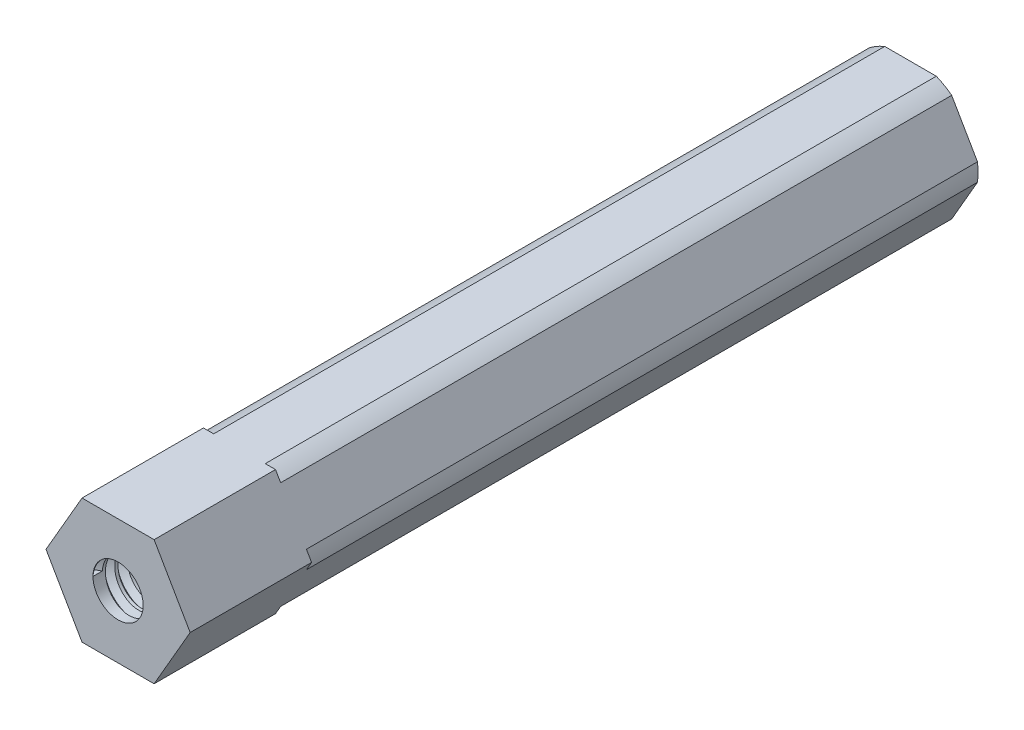
SolidWorks part; units mm, degrees
material "7075-T6 (SN)"
ref_plane "Alzado" through (0, 0, 0) normal (0, 0, 1) x (1, 0, 0)
ref_plane "Planta" through (0, 0, 0) normal (0, 1, 0) x (1, 0, 0)
ref_plane "Vista lateral" through (0, 0, 0) normal (1, 0, 0) x (0, 0, -1)
sketch "Croquis2" plane through (0, 0, 0) normal (0, 0, 1) x (1, 0, 0)
  line L1 (3.6662, -6.35) -> (7.3323, 0)
  line L2 (7.3323, 0) -> (3.6662, 6.35)
  line L3 (3.6662, 6.35) -> (-3.6662, 6.35)
  line L4 (-3.6662, 6.35) -> (-7.3323, 0)
  line L5 (-7.3323, 0) -> (-3.6662, -6.35)
  line L6 (-3.6662, -6.35) -> (3.6662, -6.35)
  circle A0 centre (0, 0) radius 6.35 construction
  dimension "D1" = 12.7
extrude "Extrusión Hex Profile" add sketch "Croquis2" along normal mid plane 80.6132
sketch "Croquis3" plane through (0, 0, 0) normal (0, 0, 1) x (1, 0, 0)
  circle A0 centre (0, 0) radius 2.5527
  dimension "D1" = 5.1054
extrude "Tap Hole 1" cut sketch "Croquis3" against normal blind 19.05 from surface starting at face at (0, 0, 40.3066)
extrude "Tap Hole 2" cut sketch "Croquis3<3>" along normal blind 19.05 from surface starting at face at (0, 0, -40.3066)
sketch "Croquis3<3>" plane through (0, 0, 0) normal (0, 0, 1) x (1, 0, 0) same geometry as "Croquis3"
sketch "Croquis7" plane through (0, 0, 0) normal (0, 0, 1) x (1, 0, 0)
  circle A0 centre (0, 0) radius 6.8707
  dimension "D1" = 13.7414
extrude "ThunderHex" cut sketch "Croquis7" along normal offset from surface (68.2625 mm away) 12.3508 from surface flip side to cut up to face at (2.5527, 0, 40.3066) starting at face at (2.5527, 0, -40.3066)
sketch "Croquis8" plane through (0, 0, 0) normal (0, 1, 0) x (1, 0, 0)
  line L0 (0, -40.3066) -> (-5.5563, -40.3066) construction
  line L1 (3.6662, -40.3066) -> (-3.6662, -40.3066) construction
  line L3 (0, -40.3066) -> (0, 0) construction
  line L4 (-5.5563, -40.3066) -> (-6.35, -39.5129)
  line L5 (-6.35, -39.5129) -> (-6.35, -38.7191)
  line L6 (-6.35, -38.7191) -> (-5.9055, -38.7191)
  line L7 (-5.9055, -38.7191) -> (-5.9055, -37.1316)
  line L8 (-5.9055, -37.1316) -> (-12.7, -37.1316)
  line L9 (-12.7, -37.1316) -> (-12.7, -40.3066)
  line L10 (-12.7, -40.3066) -> (-5.5563, -40.3066)
  line L11 (-3.6662, -40.3066) -> (-7.3323, -40.3066) construction
  dimension "D1" = 11.811
  dimension "D2" = 12.7
  dimension "D3" = 45
  dimension "D4" = 0.7937
  dimension "D6" = 0.7937
  dimension "D7" = 3.175
  dimension "D8" = 25.4
revolve "Retaining Ring 1" [suppressed] cut sketch "Croquis8" angle 360 about L3
sketch "Croquis9" plane through (0, 0, 0) normal (0, -1, 0) x (1, 0, 0)
  line L0 (0, -40.3066) -> (-5.5563, -40.3066) construction
  line L3 (0, -40.3066) -> (0, 0) construction
  line L4 (-5.5563, -40.3066) -> (-6.35, -39.5129)
  line L5 (-6.35, -39.5129) -> (-6.35, -38.7191)
  line L6 (-6.35, -38.7191) -> (-5.9055, -38.7191)
  line L7 (-5.9055, -38.7191) -> (-5.9055, -37.1316)
  line L8 (-5.9055, -37.1316) -> (-12.7, -37.1316)
  line L9 (-12.7, -37.1316) -> (-12.7, -40.3066)
  line L10 (-12.7, -40.3066) -> (-5.5563, -40.3066)
  line L12 (-2.6237, -40.3066) -> (2.6237, -40.3066) construction
  line L13 (-6.8111, -40.3066) -> (-4.1874, -40.3066) construction
  dimension "D1" = 11.811
  dimension "D2" = 12.7
  dimension "D3" = 45
  dimension "D4" = 0.7937
  dimension "D6" = 0.7937
  dimension "D7" = 3.175
  dimension "D8" = 25.4
revolve "Retaining Ring 2" [suppressed] cut sketch "Croquis9" angle 360 about L3
sketch "Croquis10" plane through (0, 0, 0) normal (0, 1, 0) x (1, 0, 0)
  line L0 (0, -40.3066) -> (0, 0) construction
  line L1 (3.6662, -40.3066) -> (-3.6662, -40.3066) construction
  line L2 (0, -40.3066) -> (-5.5563, -40.3066) construction
  line L3 (-3.6662, -40.3066) -> (-7.3323, -40.3066) construction
  line L4 (-5.5563, -40.3066) -> (-6.35, -39.5129)
  line L5 (-6.35, -39.5129) -> (-6.35, -32.3564)
  line L6 (-6.35, -32.3564) -> (-9.525, -32.3564)
  line L7 (-9.525, -32.3564) -> (-9.525, -40.3066)
  line L8 (-9.525, -40.3066) -> (-5.5563, -40.3066)
  dimension "D2" = 12.7
  dimension "D1" = 45
  dimension "D3" = 0.7937
  dimension "D4" = 7.9502
  dimension "D5" = 19.05
revolve "Round End 1" [suppressed] cut sketch "Croquis10" angle 360 about L0
sketch "Croquis12" plane through (0, 0, 0) normal (0, -1, 0) x (1, 0, 0)
  line L0 (0, -40.3066) -> (0, 0) construction
  line L2 (0, -40.3066) -> (-5.5563, -40.3066) construction
  line L4 (-5.5563, -40.3066) -> (-6.35, -39.5129)
  line L5 (-6.35, -39.5129) -> (-6.35, -32.3564)
  line L6 (-6.35, -32.3564) -> (-9.525, -32.3564)
  line L7 (-9.525, -32.3564) -> (-9.525, -40.3066)
  line L8 (-9.525, -40.3066) -> (-5.5563, -40.3066)
  line L9 (-2.6237, -40.3066) -> (2.6237, -40.3066) construction
  dimension "D1" = 45
  dimension "D3" = 0.7937
  dimension "D4" = 7.9502
  dimension "D2" = 12.7
  dimension "D5" = 19.05
revolve "Round End 2" [suppressed] cut sketch "Croquis12" angle 360 about L0
thread "Rosca1" pitch 1.27 method cut profile "Perfil de rosca1" start angle 0, offset 0, length 0, pitch 1.27, diameter 5.1054
ref_plane "Plano1" through (-2.5527, 0, 40.3066) normal (0, -1, 0) x (-1, 0, 0)
sketch "Perfil de rosca1" plane through (-2.5527, 0, 40.3066) normal (0, -1, 0) x (-1, 0, 0)
  line L0 (0, 0) -> (0, 1.27) construction
  line L1 (0, 0) -> (0.6874, 0.3969)
  line L2 (0.6874, 0.3969) -> (0.6874, 0.5556)
  line L3 (0.6874, 0.5556) -> (0, 0.9525)
  line L4 (0.6874, 0.4762) -> (0, 0.4762) construction
  line L11 (0, 0) -> (0, 0.9525)
  point P2 (0, 0)
  dimension "Pitch" = 1.27
  dimension "Profile_Angle" = 60
  dimension "Profile_Land" = 0.1588
  dimension "Profile_Height" = 0.6874
thread "Rosca2" pitch 1.27 method cut profile "Perfil de rosca2" start angle 0, offset 0, length 0, pitch 1.27, diameter 5.1054
ref_plane "Plano2" through (2.5527, 0, -40.3066) normal (0, -1, 0) x (1, 0, 0)
sketch "Perfil de rosca2" plane through (2.5527, 0, -40.3066) normal (0, -1, 0) x (1, 0, 0)
  line L0 (0, 0) -> (0, 1.27) construction
  line L1 (0, 0) -> (0.6874, 0.3969)
  line L2 (0.6874, 0.3969) -> (0.6874, 0.5556)
  line L3 (0.6874, 0.5556) -> (0, 0.9525)
  line L4 (0.6874, 0.4762) -> (0, 0.4762) construction
  line L11 (0, 0) -> (0, 0.9525)
  point P2 (0, 0)
  dimension "Pitch" = 1.27
  dimension "Profile_Angle" = 60
  dimension "Profile_Land" = 0.1588
  dimension "Profile_Height" = 0.6874
equation "\"HexOD\"= 0.5pulgadas"
equation "\"Largo\"= 3.17375pulgadas"
equation "\"D1@Croquis2\"=\"HexOD\""
equation "\"D1@Extrusión Hex Profile\" = \"Largo\""
equation "\"TapHole\"= IIF ( \"HexOD\" = 0.5pulgadas , 0.2010pulgadas , 0.190pulgadas )"
equation "\"D1@Croquis3\"=\"TapHole\""
equation "\"ProTapHole\"= 0.75pulgadas"
equation "\"D1@Tap Hole 1\" = \"ProTapHole\""
equation "\"D1@Tap Hole 2\" = \"ProTapHole\""
equation "\"ThunderHex\"= IIF ( \"HexOD\" = 0.5pulgadas , 0.541pulgadas , 0.4035pulgadas )"
equation "\"D1@Croquis7\"=\"ThunderHex\""
equation "\"D2@Croquis8\"=\"HexOD\""
equation "\"D1@Croquis8\"=if(\"HexOD\"=0.5pulgadas, 0.465pulgadas, 0.35pulgadas )"
equation "\"D2@Croquis9\"=\"HexOD\""
equation "\"D1@Croquis9\"=if(\"HexOD\"=0.5pulgadas, 0.465pulgadas, 0.35pulgadas )"
equation "\"D8@Croquis8\"=\"HexOD\"*2"
equation "\"D8@Croquis9\"=\"HexOD\"*2"
equation "\"D5@Croquis10\"=\"HexOD\"*1.5"
equation "\"D5@Croquis12\"=\"HexOD\"*1.5"
equation "\"D4@Croquis10\"=if( \"D2@Croquis10\"=<0.375, 0.28, 0.313)"
equation "\"D4@Croquis12\"=if( \"D2@Croquis10\"=<0.375, 0.28, 0.313)"
